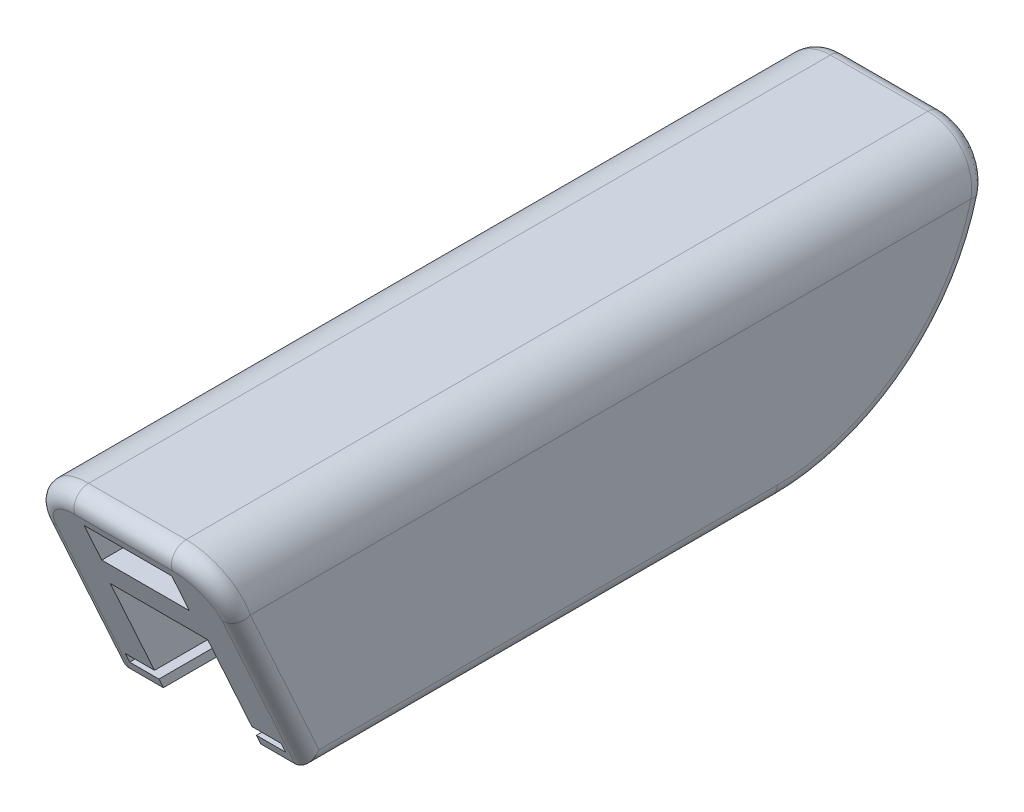
SolidWorks part; units mm, degrees
material "PA Type 6"
ref_plane "Plan de face" through (0, 0, 0) normal (0, 0, 1) x (1, 0, 0)
ref_plane "Plan de dessus" through (0, 0, 0) normal (0, 1, 0) x (1, 0, 0)
ref_plane "Plan de droite" through (0, 0, 0) normal (1, 0, 0) x (0, 0, -1)
sketch "Esquisse1" plane through (0, 0, 0) normal (0, 0, 1) x (1, 0, 0)
  line L0 (0, 0) -> (0, 60.617) construction
  line L1 (5, 24.9472) -> (-5, 24.9472)
  line L2 (-10, 19.9472) -> (-10, 2.9472)
  line L3 (10, 19.9472) -> (10, 2.9472)
  line L4 (-10, 2.9472) -> (-5, 2.9472)
  line L5 (10, 2.9472) -> (5, 2.9472)
  line L6 (-5, 2.9472) -> (-5, 3.9472)
  line L7 (5, 2.9472) -> (5, 3.9472)
  line L8 (-5, 3.9472) -> (-8, 3.9472)
  line L9 (5, 3.9472) -> (8, 3.9472)
  line L10 (-8, 3.9472) -> (-8, 4.9472)
  line L11 (8, 3.9472) -> (8, 4.9472)
  line L12 (-8, 4.9472) -> (-5, 4.9472)
  line L13 (8, 4.9472) -> (5, 4.9472)
  line L14 (-5, 4.9472) -> (-5, 14.9472)
  line L15 (5, 4.9472) -> (5, 14.9472)
  line L16 (-5, 14.9472) -> (5, 14.9472)
  line L17 (4.5, 21.9472) -> (-4.5, 21.9472)
  line L18 (-4.5, 21.9472) -> (-4.5, 17.9472)
  line L19 (4.5, 21.9472) -> (4.5, 17.9472)
  line L20 (-4.5, 17.9472) -> (4.5, 17.9472)
  arc A0 (-10, 19.9472) -> (-5, 24.9472) centre (-5, 19.9472) cw
  arc A1 (10, 19.9472) -> (5, 24.9472) centre (5, 19.9472) ccw
  point P6 (0, 24.9472)
  point P21 (0, 14.9472)
  point P24 (0, 21.9472)
  point P27 (0, 17.9472)
  point P29 (-10, 24.9472)
  point P32 (10, 24.9472)
  dimension "D12" = 5
  dimension "D1" = 10
  dimension "D2" = 10
  dimension "D3" = 16
  dimension "D4" = 9
  dimension "D5" = 3
  dimension "D6" = 4
  dimension "D7" = 3
  dimension "D8" = 1
  dimension "D9" = 1
  dimension "D10" = 12
  dimension "D11" = 20
extrude "Extrusion1" add sketch "Esquisse1" along normal blind 80
sketch "Esquisse2" plane through (10, 0, 0) normal (1, 0, 0) x (0, 0, -1)
  line L0 (0, 2.9472) -> (0, 19.9472) construction
  line L1 (-80, 2.9472) -> (0, 2.9472) construction
  line L2 (0, 24.9472) -> (0, 2.9472)
  line L3 (0, 2.9472) -> (-22, 2.9472)
  arc A0 (-22, 2.9472) -> (0, 24.9472) centre (-22, 24.9472) ccw
extrude "Enlèv. mat.-Extru.1" cut sketch "Esquisse2" against normal through all
sketch "Esquisse3" plane through (10, 0, 0) normal (1, 0, 0) x (0, 0, -1)
  line L0 (-80, 24.9472) -> (-70, 2.9472)
  line L1 (-80, 2.9472) -> (-22, 2.9472) construction
  line L2 (-70, 2.9472) -> (-80, 2.9472)
  line L3 (-80, 2.9472) -> (-80, 24.9472)
  dimension "D1" = 10
extrude "Enlèv. mat.-Extru.2" cut sketch "Esquisse3" against normal through all
fillet "Congé1" radius 1.5 8 edges at (10, 2.9472, 46) (10, 7.7135, 8.3252) (8.9327, 23.0349, 0.0833) (0, 24.9472, 0) (-8.1222, 23.8525, 0.0272) (-10, 2.9472, 46) (-10, 7.7135, 8.3252) (-10, 11.4472, 73.8636)
